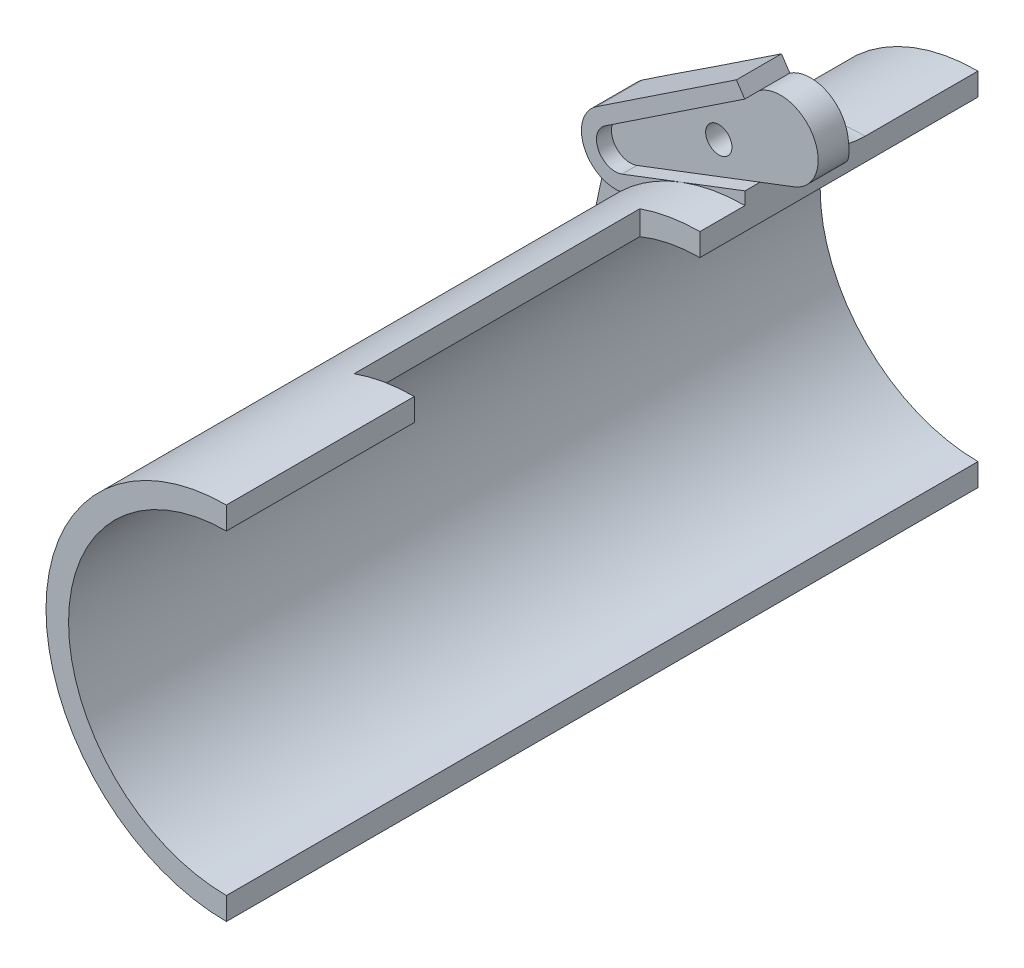
SolidWorks part; units mm, degrees
ref_plane "前视基准面" through (0, 0, 0) normal (0, 0, 1) x (1, 0, 0)
ref_plane "上视基准面" through (0, 0, 0) normal (0, 1, 0) x (1, 0, 0)
ref_plane "右视基准面" through (0, 0, 0) normal (1, 0, 0) x (0, 0, -1)
sketch "草图1" plane through (0, 0, 0) normal (0, 0, 1) x (1, 0, 0)
  line L0 (0, 24) -> (0, 21)
  line L1 (0, -21) -> (0, -24)
  arc A0 (0, 21) -> (0, -21) centre (0, 0) ccw
  arc A1 (0, 24) -> (0, -24) centre (0, 0) ccw
  dimension "D1" = 42
  dimension "D2" = 48
extrude "凸台-拉伸1" add sketch "草图1" along normal mid plane 100
sketch "草图2" plane through (0, 0, 0) normal (0, 0, 1) x (1, 0, 0)
  line L0 (0, 21) -> (0, 24) construction
  line L1 (0, 25.6908) -> (4.5189, 27.4166)
  line L2 (-0.0365, 36.2492) -> (-18.6479, 23.855)
  line L3 (-17.2622, 21.7742) -> (2.7349, 32.0876) construction
  line L4 (0, 0) -> (-6.2117, 23.1822)
  line L7 (0, 25.6908) -> (0, 24)
  line L8 (-19.7622, 21.7742) -> (-22.7706, 7.583)
  arc A0 (-18.6479, 23.855) -> (-19.7622, 21.7742) centre (-17.2622, 21.7742) ccw
  arc A1 (4.5189, 27.4166) -> (-0.0365, 36.2492) centre (2.7349, 32.0876) ccw
  arc A2 (0, 24) -> (-22.7706, 7.583) centre (0, 0) ccw
  circle A3 centre (-5.4861, 27.8476) radius 1.75
  arc A6 (0, 24) -> (0, -24) centre (0, 0) ccw construction
  dimension "D2" = 10
  dimension "D3" = 5
  dimension "D6" = 3.5
  dimension "D4" = 22.5
  dimension "D5" = 13.25
  dimension "D7" = 15
extrude "凸台-拉伸2" add sketch "草图2" along normal blind 4 from offset 25 contours A2 L7 L1 A1 L2 A0 L8 A3 region at (-0.4244, 24.8454, 0) offset against normal yes
sketch "草图3" plane through (0, 0, -25) normal (0, 0, -1) x (-1, 0, 0)
  line L0 (0.0365, 36.2492) -> (18.6479, 23.855) construction
  line L1 (0.0365, 36.2492) -> (18.6479, 23.855)
  line L2 (0, 25.6908) -> (16.3702, 19.4387)
  line L3 (0, 23.5499) -> (15.6566, 17.5703)
  line L4 (1.1451, 37.9139) -> (19.7564, 25.5196)
  line L5 (0, 23.5499) -> (0, 25.6908)
  line L6 (0.0365, 36.2492) -> (1.1451, 37.9139)
  line L7 (-5.2324, 25.5483) -> (15.6566, 17.5703) construction
  line L8 (-4.5189, 27.4166) -> (16.3702, 19.4387) construction
  arc A0 (16.3702, 19.4387) -> (18.6479, 23.855) centre (17.2622, 21.7742) ccw
  arc A3 (15.6566, 17.5703) -> (19.7564, 25.5196) centre (17.2622, 21.7742) ccw
  arc A5 (0.0365, 36.2492) -> (-4.5189, 27.4166) centre (-2.7349, 32.0876) ccw construction
  arc A6 (1.1451, 37.9139) -> (-5.2324, 25.5483) centre (-2.7349, 32.0876) ccw construction
  dimension "D1" = 2
extrude "凸台-拉伸3" add sketch "草图3" against normal blind 6
fillet "圆角2" radius 10 1 edges at (-22.7706, 7.583, -23)
fillet "圆角3" radius 10 1 edges at (-14.2105, 19.3407, -25)
sketch "草图4" plane through (0, 0, 0) normal (0, 1, 0) x (1, 0, 0)
  line L1 (-8, 13) -> (0, 13)
  line L2 (-8, 13) -> (-8, -25)
  line L3 (-8, -25) -> (0, -25)
  line L4 (0, 13) -> (0, -25)
  line L5 (0, -50) -> (0, 19) construction
  line L7 (-0.0365, 21) -> (7.7349, 21) construction
  dimension "D1" = 38
  dimension "D2" = 8
  dimension "D3" = 8
extrude "切除-拉伸1" cut sketch "草图4" along normal blind 46
